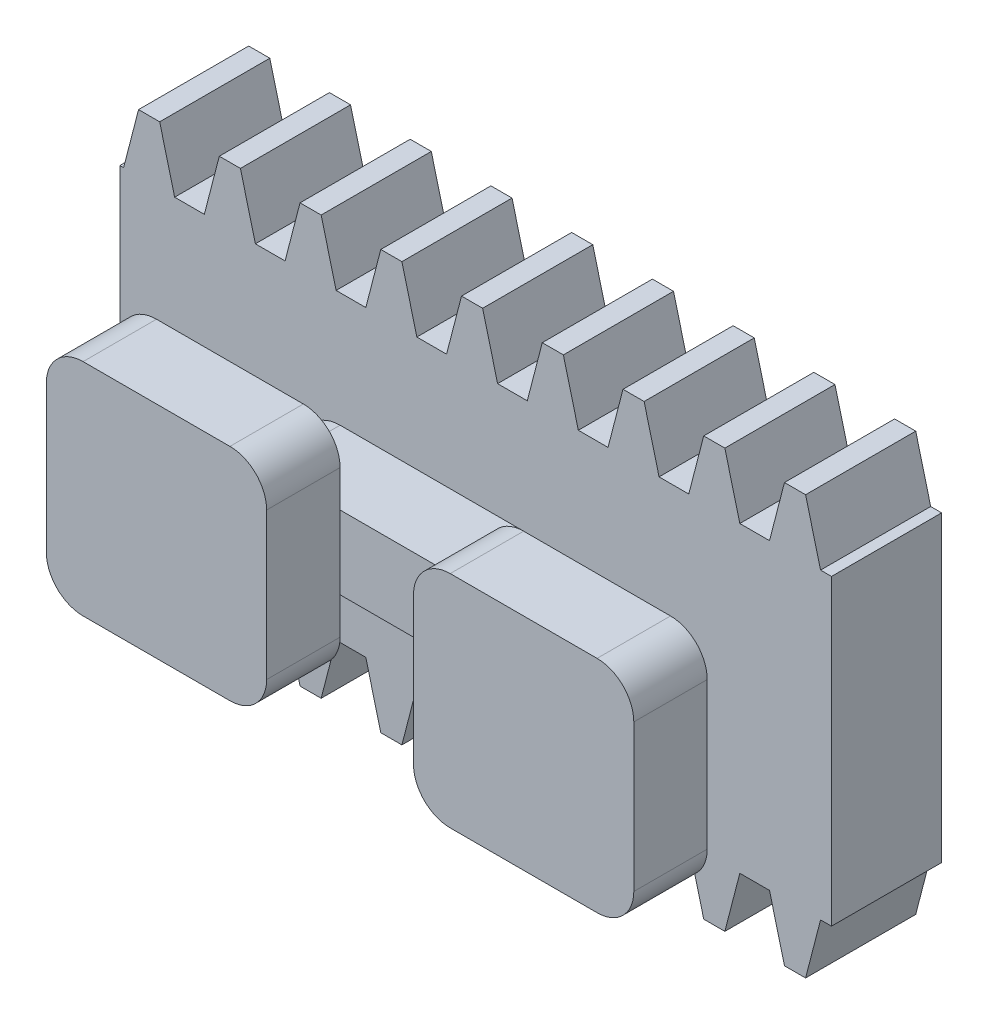
SolidWorks part; units mm, degrees
extrude "Blank" add sketch "BlankSke" against normal blind 3
sketch "BlankSke" plane through (0, 0, 0) normal (0, 0, 1) x (1, 0, 0)
  line L1 (0, 0) -> (25, 0)
  line L2 (0, 0) -> (0, 5.7)
  line L3 (0, 5.7) -> (25, 5.7)
  line L4 (25, 0) -> (25, 5.7)
  dimension "Length" = 25
ref_plane "Plane1" through (0, 0, 0) normal (0, 0, 1) x (1, 0, 0)
ref_plane "Plane2" through (0, 0, 0) normal (0, 1, 0) x (1, 0, 0)
ref_plane "Plane3" through (0, 0, 0) normal (1, 0, 0) x (0, 0, -1)
other "Configuration Table"
sketch "HoldingSke" plane through (0, 0, 0) normal (0, 1, 0) x (1, 0, 0)
  line L0 (0, 0) -> (0.1988, 1.4147)
  line L1 (-15, 0) -> (100, 0) construction
  line L2 (0, 0) -> (-2.1039, 2.3779)
  line L3 (0, 0) -> (-11.863, 4.5341)
  line L4 (0, 0) -> (8.4147, 1.9427)
  line L5 (0, 0) -> (-23.7986, -8.8762)
  line L6 (0, 0) -> (-10.5278, -7.1032)
  line L9 (-67.7845, 28.3722) -> (-43.5808, 34.6317)
  line L10 (-76.2, 3.0779) -> (-71.2, 3.0779)
  line L11 (0, 0) -> (-3, 0)
  line L12 (-76.2, 101.6) -> (-76.173, 101.6)
  line L13 (24.9733, 27.94) -> (52.9518, 28.4284)
  line L14 (24.9733, 27.94) -> (24.9743, 27.94)
  line L15 (24.9733, 27.94) -> (100.4006, 29.5858)
  circle A0 centre (0, 0) radius 19.05
  circle A1 centre (0, 0) radius 2.5
  circle A2 centre (0, 0) radius 12.7
  dimension "Num_teeth" = 13
  dimension "Width" = 3
  dimension "Length" = 25
  dimension "Pitch_height" = 5
sketch "TooCutSkeIll" plane through (0, 0, 0) normal (0, 0, 1) x (1, 0, 0)
  line L0 (-0.8064, 5.679) -> (-0.4386, 4.2569)
  line L1 (-0.2682, 4.125) -> (0.2682, 4.125)
  line L2 (0.4386, 4.2569) -> (0.8064, 5.679)
  line L3 (25, 5.7) -> (0, 5.7) construction
  line L4 (0, 0) -> (0, 64.897) construction
  line L5 (-13.208, 5) -> (12.954, 5) construction
  line L6 (0, 0) -> (25, 0) construction
  line L7 (0.6308, 5) -> (0.6308, 48.7463) construction
  line L8 (-0.6308, 5) -> (-0.6308, 48.7463) construction
  line L9 (0.8335, 5.7) -> (0.8335, 5.7254)
  line L10 (-0.8335, 5.7) -> (-0.8335, 5.7254)
  line L11 (-0.8335, 5.7254) -> (0.8335, 5.7254)
  arc A0 (0.2682, 4.125) -> (0.4386, 4.2569) centre (0.2682, 4.301) ccw
  arc A1 (-0.4386, 4.2569) -> (-0.2682, 4.125) centre (-0.2682, 4.301) ccw
  arc A2 (0.8335, 5.7) -> (0.8064, 5.679) centre (0.8335, 5.672) ccw
  arc A3 (-0.8064, 5.679) -> (-0.8335, 5.7) centre (-0.8335, 5.672) ccw
  dimension "Addendum_plus" = 0.7254
  dimension "Pitch_height" = 5
  dimension "Pressure_angle" = 14.5
  dimension "Gap_width" = 1.2616
  dimension "Dedendum" = 0.875
extrude "ToothCutIll" [suppressed] cut sketch "TooCutSkeIll" against normal through all
sketch "TooCutSkeSim" plane through (0, 0, 0) normal (0, 0, 1) x (1, 0, 0)
  line L0 (0.4045, 4.125) -> (-0.4045, 4.125)
  line L1 (0.8184, 5.7254) -> (0.4045, 4.125)
  line L2 (0, 17.4625) -> (0, 53.467) construction
  line L3 (0.8184, 5.7254) -> (-0.8184, 5.7254)
  line L6 (-0.8184, 5.7254) -> (-0.4045, 4.125)
  line L9 (-0.6308, 5) -> (0.6308, 5) construction
  line L10 (0, 0) -> (25, 0) construction
  line L11 (0.6308, 5) -> (0.6308, 53.467) construction
  line L12 (-0.6308, 5) -> (-0.6308, 53.467) construction
  dimension "Addendum_plus" = 0.7254
  dimension "Pitch_height" = 5
  dimension "Pressure_angle" = 14.5
  dimension "Gap_width" = 1.2616
  dimension "Dedendum" = 0.875
extrude "ToothCutSim" cut sketch "TooCutSkeSim" against normal through all
pattern_linear "TeethCuts" count 13 spacing 2.1991 along (1, 0, 0) of "ToothCutIll", "ToothCutSim"
mirror "镜向1" [suppressed]
mirror "镜向2" about plane through (0, 0, -3) normal (0, -1, 0) of "Blank", "ToothCutSim", "TeethCuts"
sketch "草图1" plane through (0, 0, 0) normal (-1, 0, 0) x (0, 0, 1)
  line L1 (0, 4.125) -> (0, -4.125) construction
  line L4 (-3, 0) -> (0, 0) construction
  line L5 (-3, 4.125) -> (-3, -4.125) construction
  line L7 (0, -3) -> (0, 3)
  line L8 (0, 3) -> (-2, 3.5)
  line L9 (-2, 3.5) -> (-2, -3.5)
  line L10 (0, -3) -> (-2, -3.5)
  point P11 (-2.5, 0)
  point P12 (-2, 0)
  dimension "D1" = 3
  dimension "D2" = 3.5
  dimension "D3" = 2
sketch "草图2" plane through (0, 0, -3) normal (0, 0, -1) x (-1, 0, 0)
  line L0 (0, 0) -> (-25, 0) construction
  line L1 (0, 4.125) -> (0, -4.125) construction
  line L2 (-25, -5.692) -> (-25, 5.692) construction
  circle A0 centre (-12.5, 0) radius 1.5
  dimension "D1" = 3
extrude "凸台-拉伸1" add sketch "草图2" along normal blind 1.5
sketch "草图3" plane through (0, 0, -4.5) normal (0, 0, -1) x (-1, 0, 0)
  circle A0 centre (-12.5, 0) radius 0.5
  dimension "D1" = 1
extrude "切除-拉伸3" cut sketch "草图3" against normal through all
sketch "草图4" plane through (0, 0, -3) normal (0, 0, -1) x (-1, 0, 0)
  line L0 (-12.5, 0) -> (-21.8848, 0) construction
  line L1 (-12.5, 0) -> (-2.5, 0) construction
  line L2 (-21.8848, 2.1496) -> (-21.8848, -2.1496)
  line L3 (-22.3956, 4.125) -> (-22.803, 5.7) construction
  line L4 (-2.5, 4.125) -> (-2.5, -4.125)
  line L6 (-1.7946, -4.125) -> (-2.6036, -4.125) construction
  line L7 (-22.3956, -4.125) -> (-22.803, -5.7) construction
  line L9 (-1.7946, 4.125) -> (-2.6036, 4.125) construction
  line L10 (-21.8848, 2.1496) -> (-21.8848, 5.9598)
  line L11 (-21.8848, 5.9598) -> (-25.6774, 5.9598)
  line L12 (-25.6774, 5.9598) -> (-25.6774, -6.5792)
  line L13 (-25.6774, -6.5792) -> (-21.8848, -6.5792)
  line L14 (-21.8848, -6.5792) -> (-21.8848, -2.1496)
  line L15 (-2.5, 4.125) -> (-2.5, 6.4022)
  line L16 (-2.5, 6.4022) -> (0, 6.4022)
  line L17 (0, 6.4022) -> (0, -6.0736)
  line L18 (0, -6.0736) -> (-2.5, -6.0736)
  line L19 (-2.5, -6.0736) -> (-2.5, -4.125)
  dimension "D2" = 10
extrude "切除-拉伸4" cut sketch "草图4" against normal blind 10
sketch "草图5" plane through (0, 0, 0) normal (0, 0, 1) x (1, 0, 0)
  line L0 (2.5, 2) -> (21.8848, 2)
  line L1 (2.5, 4.125) -> (2.5, -4.125) construction
  line L2 (21.8848, -4.125) -> (21.8848, 4.125) construction
  line L3 (21.8848, 2) -> (21.8848, -2)
  line L4 (21.8848, -2) -> (2.5, -2)
  line L5 (2.5, -2) -> (2.5, 2)
  point P8 (2.5, 0)
  point P9 (21.8848, 0)
  dimension "D1" = 4
sketch "草图6" plane through (0, 0, 0) normal (0, 0, 1) x (1, 0, 0)
  line L0 (1.1742, 0) -> (24.2349, 0) construction
  line L1 (7.5, 1) -> (7.5, -1)
  line L2 (7.5, -1) -> (17.5, -1)
  line L3 (17.5, -1) -> (17.5, 1)
  line L4 (17.5, 1) -> (7.5, 1)
  point P2 (17.5, 0)
  point P4 (12.5, 0)
  point P5 (7.5, 0)
  dimension "D1" = 2
  dimension "D2" = 10
  dimension "D3" = 5
extrude "凸台-拉伸3" add sketch "草图6" along normal blind 2
sketch "草图7" plane through (0, 0, 2) normal (0, 0, 1) x (1, 0, 0)
  line L0 (4.5, 3) -> (10.5, 3)
  line L1 (20.5, 3) -> (20.5, -3)
  line L2 (20.5, -3) -> (14.5, -3)
  line L3 (4.5, -3) -> (4.5, 3)
  line L5 (17.5, 1) -> (7.5, 1) construction
  line L6 (7.5, -1) -> (17.5, -1) construction
  line L7 (7.5, 1) -> (7.5, -1) construction
  line L8 (17.5, -1) -> (17.5, 1) construction
  line L9 (10.5, 3) -> (10.5, -3)
  line L10 (14.5, 3) -> (14.5, -3)
  line L11 (14.5, 3) -> (20.5, 3)
  line L12 (10.5, -3) -> (4.5, -3)
  dimension "D1" = 2
  dimension "D2" = 2
  dimension "D3" = 3
  dimension "D4" = 3
  dimension "D5" = 6
  dimension "D6" = 6
extrude "凸台-拉伸4" add sketch "草图7" along normal blind 2
fillet "圆角1" radius 1 4 edges at (17.5, -1, 1) (7.5, -1, 1) (17.5, 1, 1) (7.5, 1, 1)
fillet "圆角2" radius 1 8 edges at (4.5, -3, 3) (4.5, 3, 3) (10.5, 3, 3) (10.5, -3, 3) (14.5, -3, 3) (14.5, 3, 3) (20.5, 3, 3) (20.5, -3, 3)
equation "' \"Module@HoldingSke\" = 6.35"
equation "' \"Num_teeth@HoldingSke\" = 12"
equation "' \"Ap@HoldingSke\" =  20"
equation "' \"Ap@HoldingSke\" = 20"
equation "' \"Width@HoldingSke\" = 0.25 * 25.4"
equation "' \"Show_teeth@HoldingSke\" = 500"
equation "' \"Backlash@HoldingSke\" = 0.009 * 25.4"
equation "' \"Addendum_fac@HoldingSke\" = 1.0"
equation "' \"Dedendum_fac@HoldingSke\" = 1.25"
equation "' \"Dedendum_add@HoldingSke\" = 0.00005 * 25.4"
equation "' \"Clearance_fac@HoldingSke\" = 0.25"
equation "' \"Pitch_height@HoldingSke\" = 1 * 25.4"
equation "' \"Length@HoldingSke\" = 4.71 * 25.4"
equation "\"Pitch@HoldingSke\" = 1 / \"Module@HoldingSke\""
equation "\"MPH@HoldingSke\" = \"Dedendum_fac@HoldingSke\" / \"Pitch@HoldingSke\" + 2 * \"Dedendum_add@HoldingSke\" + 0.002 * 25.4"
equation "\"MPH@HoldingSke\" = ((sgn( \"MPH@HoldingSke\" - \"Pitch_height@HoldingSke\")+1)*( \"MPH@HoldingSke\" - \"Pitch_height@HoldingSke\"))/2 + \"Pitch_height@HoldingSke\""
equation "\"Blank_height@BlankSke\" = \"Pitch_height@HoldingSke\" + \"Addendum_fac@HoldingSke\"  / \"Pitch@HoldingSke\" "
equation "\"Length@BlankSke\" =  \"Length@HoldingSke\""
equation "\"Face_width@Blank\" = \"Width@HoldingSke\""
equation "\"Pressure_angle@TooCutSkeIll\" = \"Ap@HoldingSke\""
equation "\"Addendum_plus@TooCutSkeIll\" =  \"Addendum_fac@HoldingSke\"  / \"Pitch@HoldingSke\" + 0.001 *25.4"
equation "\"Dedendum@TooCutSkeIll\" = \"Dedendum_fac@HoldingSke\"  / \"Pitch@HoldingSke\""
equation "\"Pitch_height@TooCutSkeIll\" =  \"MPH@HoldingSke\""
equation "\"Gap_width@TooCutSkeIll\" = 3.14159265 / 2 / \"Pitch@HoldingSke\" + 6 * \"Backlash@HoldingSke\""
equation "\"Pressure_angle@TooCutSkeSim\" = \"Ap@HoldingSke\""
equation "\"Addendum_plus@TooCutSkeSim\" =  \"Addendum_fac@HoldingSke\"  / \"Pitch@HoldingSke\" + 0.001 * 25.4"
equation "\"Dedendum@TooCutSkeSim\" = \"Dedendum_fac@HoldingSke\"  / \"Pitch@HoldingSke\""
equation "\"Pitch_height@TooCutSkeSim\" =  \"MPH@HoldingSke\""
equation "\"Gap_width@TooCutSkeSim\" = 3.14159265 / 2 / \"Pitch@HoldingSke\" + 6 * \"Backlash@HoldingSke\""
equation "\"Root_fillet@TooCutSkeIll\" = \"Clearance_fac@HoldingSke\" / \"Pitch@HoldingSke\" + \"Dedendum_add@HoldingSke\""
equation "\"Break_rad@TooCutSkeIll\" = 0.02 / \"Pitch@HoldingSke\" * 2"
equation "\"Linear_pitch@TeethCuts\" = 3.14159265 / \"Pitch@HoldingSke\""
equation "\"Num_teeth@HoldingSke\" = int( ( \"Length@HoldingSke\" + 0 ) / (3.14159265 / \"Pitch@HoldingSke\")) + 0.9999  + 1"
equation " \"Num_teeth@TeethCuts\" = int( \"Show_teeth@HoldingSke\" ) + 1"
equation " \"Num_teeth@TeethCuts\" = ((sgn( \"Num_teeth@TeethCuts\" - \"Num_teeth@HoldingSke\" )-1)*( \"Num_teeth@TeethCuts\" - \"Num_teeth@HoldingSke\" ))/-2+ \"Num_teeth@HoldingSke\""
equation " \"Num_teeth@TeethCuts\" = ((sgn( \"Num_teeth@TeethCuts\" - 2.0)+1)*( \"Num_teeth@TeethCuts\" - 2.0))/2 +2.0"
